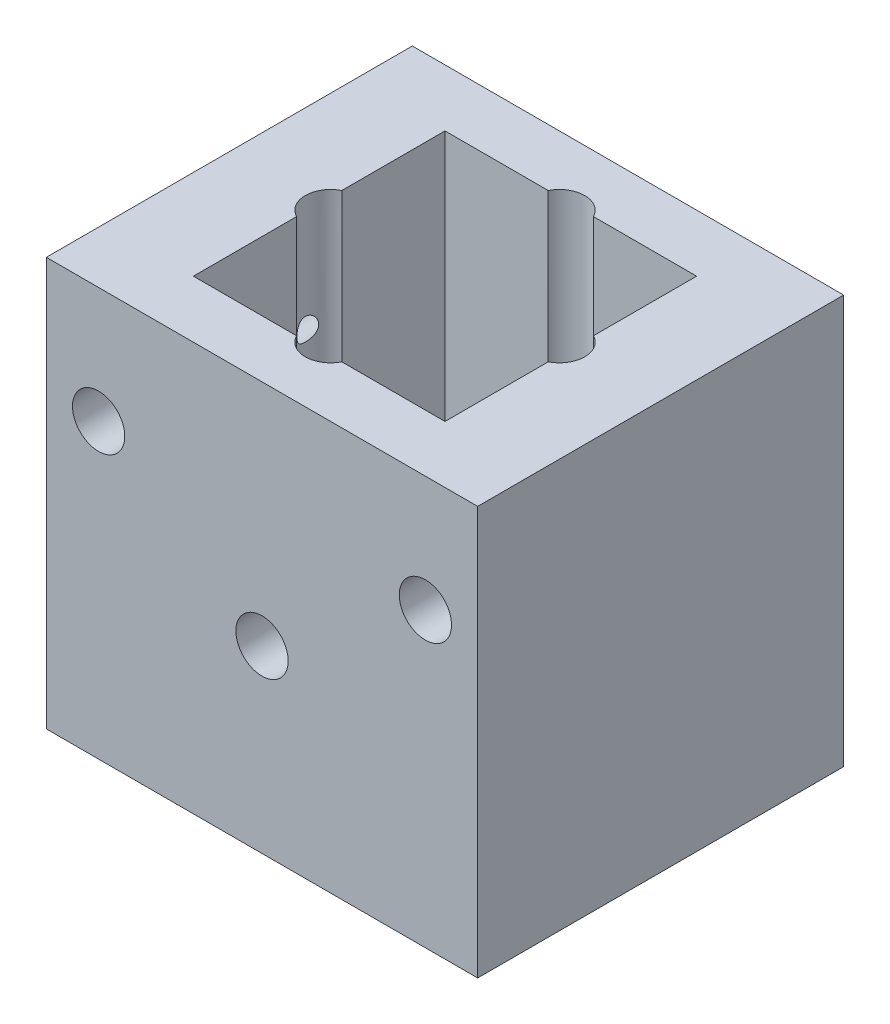
SolidWorks part; units mm, degrees
ref_plane "前视基准面" through (0, 0, 0) normal (0, 0, 1) x (1, 0, 0)
ref_plane "上视基准面" through (0, 0, 0) normal (0, 1, 0) x (1, 0, 0)
ref_plane "右视基准面" through (0, 0, 0) normal (1, 0, 0) x (0, 0, -1)
sketch "草图1" plane through (0, 0, 0) normal (0, 1, 0) x (1, 0, 0)
  line L0 (0, 0) -> (0, 7.7) construction
  line L1 (0, 0) -> (0, -7.7) construction
  line L2 (0, 0) -> (7.7, 0) construction
  line L3 (0, 0) -> (-7.7, 0) construction
  line L4 (0, 7.7) -> (7.7, 7.7)
  line L5 (7.7, 7.7) -> (7.7, 0)
  line L6 (7.7, -7.7) -> (0, -7.7)
  line L7 (-7.7, -7.7) -> (-7.7, 0)
  line L8 (-7.7, 7.7) -> (0, 7.7)
  line L9 (-7.7, 0) -> (-7.7, 7.7)
  line L10 (-7.7, -7.7) -> (0, -7.7)
  line L11 (7.7, -7.7) -> (7.7, 0)
  line L12 (-7.7, -7.7) -> (-7.7, -11.2)
  line L13 (7.7, -7.7) -> (7.7, -11.2)
  line L14 (-7.7, 11.2) -> (-7.7, 7.7)
  line L15 (7.7, 7.7) -> (7.7, 11.2)
  line L19 (-7.7, 11.2) -> (7.7, 11.2)
  line L22 (7.7, -11.2) -> (-7.7, -11.2)
  line L28 (-7.7, -7.7) -> (-4.7, -7.7)
  line L30 (7.7, 11.2) -> (13.2, 11.2)
  line L32 (13.2, 11.2) -> (13.2, -11.2)
  line L33 (7.7, -11.2) -> (13.2, -11.2)
  line L34 (-7.7, -11.2) -> (-13.2, -11.2)
  line L35 (-13.2, -11.2) -> (-13.2, 11.2)
  line L36 (-13.2, 11.2) -> (-7.7, 11.2)
extrude "凸台-拉伸2" add sketch "草图1" along normal blind 3 contours L6 L11 L5 L4 L8 L9 L7 L10 | L8 L4 | L6 L10 region at (0, 0, -9.45) region at (0, 0, 0) region at (0, 0, 9.45)
extrude "凸台-拉伸3" add sketch "草图1<4>" along normal blind 10 separate body contours L22 | L19 region at (0, 0, -9.45) region at (0, 0, 9.45)
sketch "草图1<4>" plane through (0, 0, 0) normal (0, 1, 0) x (1, 0, 0) same geometry as "草图1"
extrude "凸台-拉伸4" add sketch "草图1<5>" along normal blind 25 contours L36 L35 L34 L7 L9 | L33 L32 L30 L5 L11 | L10 | L6 | L4 | L8 region at (0, 0, -9.45) region at (10.45, 0, 0) region at (-10.45, 0, 0) region at (0, 0, 9.45)
sketch "草图1<5>" plane through (0, 0, 0) normal (0, 1, 0) x (1, 0, 0) same geometry as "草图1"
sketch "草图3" plane through (0, 0, -19.6) normal (0, 0, -1) x (-1, 0, 0)
  line L0 (13.2, 13) -> (13.2, 16)
  line L1 (-13.2, 25) -> (-13.2, 0) construction
  line L2 (-13.2, 8) -> (-13.2, 13)
  line L3 (0, 17.91) -> (10, 17.91)
  line L4 (13.2, 25) -> (13.2, 0) construction
  line L5 (13.2, 8) -> (13.2, 13)
  line L6 (0, 0) -> (0, 11) construction
  line L7 (-13.2, 8) -> (-7.5, 8) construction
  line L8 (13.2, 8) -> (7.5, 8) construction
  line L9 (17.5, 0) -> (-17.5, 0) construction
  line L10 (0, 17.91) -> (0, 11)
  line L11 (0, 17.91) -> (-10, 17.91)
  circle A0 centre (0, 11) radius 1.6
  circle A1 centre (-10, 17.91) radius 1.6
  circle A2 centre (10, 17.91) radius 1.6
  point P21 (0, 0)
  point P22 (0, 0)
  point P23 (0, 0)
  point P24 (0, 0)
extrude "切除-拉伸2" cut sketch "草图3" against normal through all contours A2 | A0 | A1 region at (-10, 19.4647, -19.6) region at (-1.0994, 12.0994, -19.6) region at (11.5547, 17.91, -19.6)
sketch "草图8" plane through (-13.2, 0, 0) normal (-1, 0, 0) x (0, 0, 1)
  line L0 (10, 10) -> (10, 3)
  line L1 (0, 3) -> (10, 3)
  line L2 (10, 10) -> (10, 13)
  line L3 (-10, 3) -> (0, 3)
  line L10 (-10, 3) -> (-10, 13)
  line L11 (-10, 13) -> (10, 13)
sketch "草图9" plane through (0, 0, 0) normal (0, -1, 0) x (1, 0, 0)
  line L0 (0, 0) -> (-7, 0) construction
  line L1 (0, 0) -> (7, 0) construction
  line L2 (0, 0) -> (0, -7) construction
  line L3 (0, 0) -> (0, 7) construction
  line L4 (0, 7) -> (-7, 7) construction
  line L5 (-7, 7) -> (-7, 0) construction
  line L6 (-7, 0) -> (-7, -7) construction
  line L7 (-7, -7) -> (0, -7) construction
  line L8 (7, -7) -> (7, 0) construction
  line L9 (7, -7) -> (0.5896, -7) construction
  line L10 (7, 0) -> (7, 7) construction
  line L11 (7, 7) -> (0, 7) construction
  line L12 (-7, 7) -> (7, -7) construction
  line L13 (-7, -7) -> (7, 7) construction
  line L14 (0, 0) -> (-4.9497, 4.9497) construction
  line L15 (0, 0) -> (-4.9497, -4.9497) construction
  line L16 (0, 0) -> (4.9497, -4.9497) construction
  line L17 (0, 0) -> (4.9497, 4.9497) construction
  circle A0 centre (-4.9497, -4.9497) radius 1.3
  circle A1 centre (4.9497, -4.9497) radius 1.3
  circle A2 centre (4.9497, 4.9497) radius 1.3
  circle A3 centre (-4.9497, 4.9497) radius 1.3
  circle A4 centre (0, 0) radius 3
  circle A5 centre (7, 0) radius 1.55
  circle A6 centre (0, 7) radius 1.55
  circle A7 centre (0, -7) radius 1.55
  circle A8 centre (-7, 0) radius 1.55
extrude "切除-拉伸6" cut sketch "草图9" against normal through all
sketch "草图10" plane through (0, 0, -11.2) normal (0, 0, -1) x (-1, 0, 0)
  circle A0 centre (10, 17.91) radius 3
  circle A1 centre (0, 11) radius 3
  circle A2 centre (-10, 17.91) radius 3
extrude "切除-拉伸7" cut sketch "草图10" against normal blind 2
